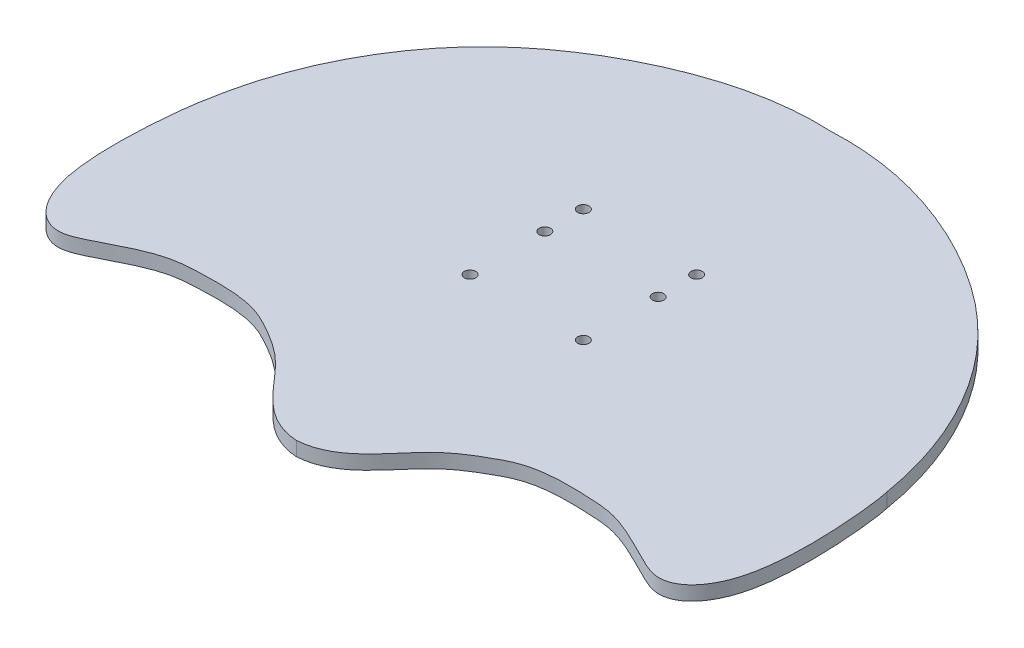
SolidWorks part; units mm, degrees
material "6061-T6 (SS)"
ref_plane "Front Plane" through (0, 0, 0) normal (0, 0, 1) x (1, 0, 0)
ref_plane "Top Plane" through (0, 0, 0) normal (0, 1, 0) x (1, 0, 0)
ref_plane "Right Plane" through (0, 0, 0) normal (1, 0, 0) x (0, 0, -1)
sketch "Sketch3" plane through (0, 0, 0) normal (0, 1, 0) x (1, 0, 0)
  line L0 (0, 0) -> (0, 159.1899) construction
  line L1 (0, 0) -> (0, -140.5301) construction
  line L2 (0, 0) -> (-190.5, 0) construction
  line L3 (0, 0) -> (190.5, 0) construction
  spline S0 degree 3 poles (-190.5, 0) (-184.3927, 37.537) (-157.2613, 93.9641) (-82.3875, 146.6227) (-31.3114, 160.7999) (0, 159.1899) knots 0 0 0 0 0.424401 0.65637 1 1 1 1
  spline S1 degree 3 poles (-190.5, 0) (-192.064, -4.9635) (-201.9672, -83.3146) (-174.6966, -109.29) (-151.6301, -100.568) (-131.4108, -87.7198) (-96.8436, -85.3754) (-78.6925, -86.2588) (-58.8335, -96.8794) (-37.3059, -109.9358) (-21.3496, -139.1148) (0, -140.5301) knots 0 0 0 0 0.166997 0.292321 0.319633 0.426735 0.458914 0.609242 0.64191 0.766802 1 1 1 1
  spline S2 degree 3 poles (190.5, 0) (192.064, -4.9635) (201.9672, -83.3146) (174.6966, -109.29) (151.6301, -100.568) (131.4108, -87.7198) (96.8436, -85.3754) (78.6925, -86.2588) (58.8335, -96.8794) (37.3059, -109.9358) (21.3496, -139.1148) (0, -140.5301) knots 0 0 0 0 0.166997 0.292321 0.319633 0.426735 0.458914 0.609242 0.64191 0.766802 1 1 1 1
  spline S3 degree 3 poles (190.5, 0) (184.3927, 37.537) (157.2613, 93.9641) (82.3875, 146.6227) (31.3114, 160.7999) (0, 159.1899) knots 0 0 0 0 0.424401 0.65637 1 1 1 1
  dimension "D1" = 381
  dimension "D2" = 299.72
  dimension "D3" = 159.1899
  dimension "D4" = 86.8953
  dimension "D5" = 104.4979
  dimension "D6" = 29.1616
  dimension "D7" = 92.2742
  dimension "D8" = 108.411
  dimension "D9" = 67.4883
  dimension "D10" = 43.7314
  dimension "D11" = 117.6915
  dimension "D12" = 162.2568
  dimension "D13" = 89.4522
  dimension "D14" = 140.1036
  dimension "D15" = 175.0666
  dimension "D16" = 50.2669
  dimension "D17" = 101.3666
  dimension "D18" = 138.1225
  dimension "D19" = 155.1557
  dimension "D20" = 192.0074
  dimension "D21" = 193.9268
  dimension "D23" = 76.6666
extrude "Boss-Extrude1" add sketch "Sketch3" along normal blind 7.9502 from surface starting at plane "Top Plane"
sketch "Sketch5" plane through (0, 0, 0) normal (0, -1, 0) x (1, 0, 0)
  line L0 (0, 0) -> (0, -20.32) construction
  line L1 (31.75, -52.07) -> (-31.75, -52.07)
  line L2 (31.75, -52.07) -> (31.75, 11.43)
  line L3 (31.75, 11.43) -> (-31.75, 11.43)
  line L4 (-31.75, -52.07) -> (-31.75, 11.43)
  line L5 (31.75, -52.07) -> (-31.75, 11.43) construction
  line L6 (31.75, 11.43) -> (-31.75, -52.07) construction
  line L7 (-31.75, -52.07) -> (-31.75, -30.48)
  line L8 (-31.75, -30.48) -> (31.75, -30.48) construction
  point P0 (0, -20.32)
  point P3 (0, -20.32)
  dimension "D2" = 63.5
  dimension "D3" = 63.5
  dimension "D4" = 21.59
hole_wizard "1/4 (0.25) Diameter Hole1" positions "Sketch6" profile "Sketch7" hole size "1/4" standard "ANSI Inch" end condition through all
sketch "Sketch6" plane through (0, 0, 0) normal (0, -1, 0) x (-1, 0, 0)
  point P0 (-31.75, 52.07)
  point P3 (31.75, 52.07)
  point P6 (31.75, -11.43)
  point P9 (-31.75, -11.43)
  point P12 (-31.75, 30.48)
  point P15 (31.75, 30.48)
sketch "Sketch7" plane through (31.75, 0, -52.07) normal (1, 0, 0) x (0, 0, -1)
  line L0 (0, 0) -> (0, 7.9502)
  line L1 (0, 7.9502) -> (3.175, 7.9502)
  line L2 (3.175, 7.9502) -> (3.175, 0)
  line L5 (3.175, 0) -> (0, 0)
  line L11 (0, -6.35) -> (0, 107.95) construction
  dimension "Thru Hole Dia." = 6.35
  dimension "Thru Hole Depth" = 7.9502
sketch "Sketch9" plane through (0, 7.9502, 0) normal (0, 1, 0) x (1, 0, 0)
  line L0 (102.3823, -86.0787) -> (102.3823, 130.9193)
  line L1 (-50.7649, -102.4301) -> (50.7649, -102.4301)
  spline S0 degree 3 poles (0, -140.5301) (21.3496, -139.1148) (37.3059, -109.9358) (58.8335, -96.8794) (78.6925, -86.2588) (96.8436, -85.3754) (131.4108, -87.7198) (151.6301, -100.568) (174.6966, -109.29) (201.9672, -83.3146) (192.064, -4.9635) (190.5, 0) knots 0 0 0 0 0.233198 0.35809 0.390758 0.541086 0.573265 0.680367 0.707679 0.833003 1 1 1 1 construction
  spline S1 degree 3 poles (190.5, 0) (184.3927, 37.537) (157.2613, 93.9641) (82.3875, 146.6227) (31.3114, 160.7999) (0, 159.1899) knots 0 0 0 0 0.424401 0.65637 1 1 1 1 construction
  spline S2 degree 3 poles (-190.5, 0) (-192.064, -4.9635) (-201.9672, -83.3146) (-174.6966, -109.29) (-151.6301, -100.568) (-131.4108, -87.7198) (-96.8436, -85.3754) (-78.6925, -86.2588) (-58.8335, -96.8794) (-37.3059, -109.9358) (-21.3496, -139.1148) (0, -140.5301) knots 0 0 0 0 0.166997 0.292321 0.319633 0.426735 0.458914 0.609242 0.64191 0.766802 1 1 1 1 construction
  dimension "D1" = 38.1
split line "Split Line1" [suppressed]
equation "\"Plate thickness\"=0.313"
equation "\"D1@Boss-Extrude1\"=\"Plate thickness\""
equation "\"Bracket Alignment\"= .80"
equation "\"D1@Sketch5\"=\"Bracket Alignment\""
